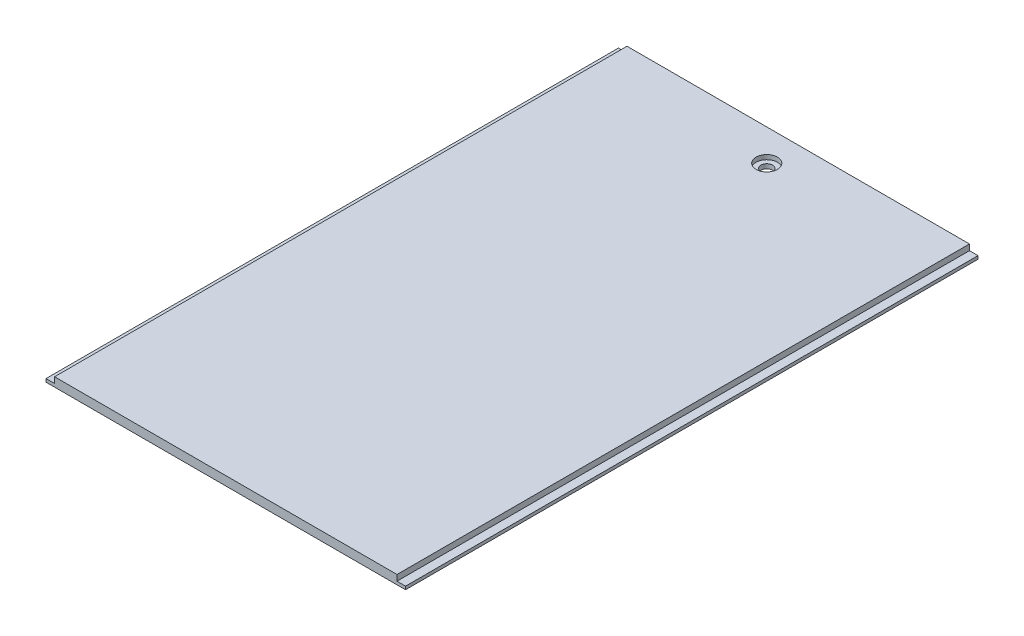
SolidWorks part; units mm, degrees
material "PLA"
ref_plane "Спереди" through (0, 0, 0) normal (0, 0, 1) x (1, 0, 0)
ref_plane "Сверху" through (0, 0, 0) normal (0, 1, 0) x (1, 0, 0)
ref_plane "Справа" through (0, 0, 0) normal (1, 0, 0) x (0, 0, -1)
sketch "Эскиз1" plane through (0, 0, 0) normal (0, 1, 0) x (1, 0, 0)
  line L1 (38.075, 63.65) -> (-38.075, 63.65)
  line L2 (38.075, 63.65) -> (38.075, -63.65)
  line L3 (38.075, -63.65) -> (-38.075, -63.65)
  line L4 (-38.075, 63.65) -> (-38.075, -63.65)
  line L5 (38.075, 63.65) -> (-38.075, -63.65) construction
  line L6 (38.075, -63.65) -> (-38.075, 63.65) construction
  point P0 (0, 0)
  dimension "D1" = 76.15
  dimension "D2" = 127.3
extrude "Бобышка-Вытянуть1" add sketch "Эскиз1" along normal blind 2
sketch "Эскиз2" plane through (0, 0, 63.65) normal (0, 0, 1) x (1, 0, 0)
  line L0 (0, 0) -> (0, -50000) construction
  line L1 (-38.075, 0) -> (-39.975, 0)
  line L2 (-38.075, 0) -> (-38.075, 0.7)
  line L3 (-38.075, 0.7) -> (-39.975, 0.7)
  line L4 (-39.975, 0) -> (-39.975, 0.7)
  line L5 (38.075, 0.7) -> (39.975, 0.7)
  line L6 (39.975, 0) -> (39.975, 0.7)
  line L7 (38.075, 0) -> (39.975, 0)
  line L8 (38.075, 0) -> (38.075, 0.7)
  dimension "D1" = 0.7
  dimension "D2" = 1.9
extrude "Бобышка-Вытянуть2" add sketch "Эскиз2" against normal up to surface (127.3 mm away) up to face at (0, 1, -63.65)
sketch "Эскиз3" plane through (0, 2, 0) normal (0, 1, 0) x (1, 0, 0)
  line L0 (0, 0) -> (0, 50000) construction
  line L1 (38.075, 63.65) -> (-38.075, 63.65) construction
  circle A0 centre (0, 56.65) radius 1.3
  dimension "D1" = 2.6
  dimension "D2" = 7
extrude "Вырез-Вытянуть1" cut sketch "Эскиз3" against normal through all
sketch "Эскиз5" plane through (0, 2, 0) normal (0, 1, 0) x (1, 0, 0)
  circle A0 centre (0, 56.65) radius 2.375
  dimension "D1" = 4.75
extrude "Вырез-Вытянуть2" cut sketch "Эскиз5" against normal blind 1
